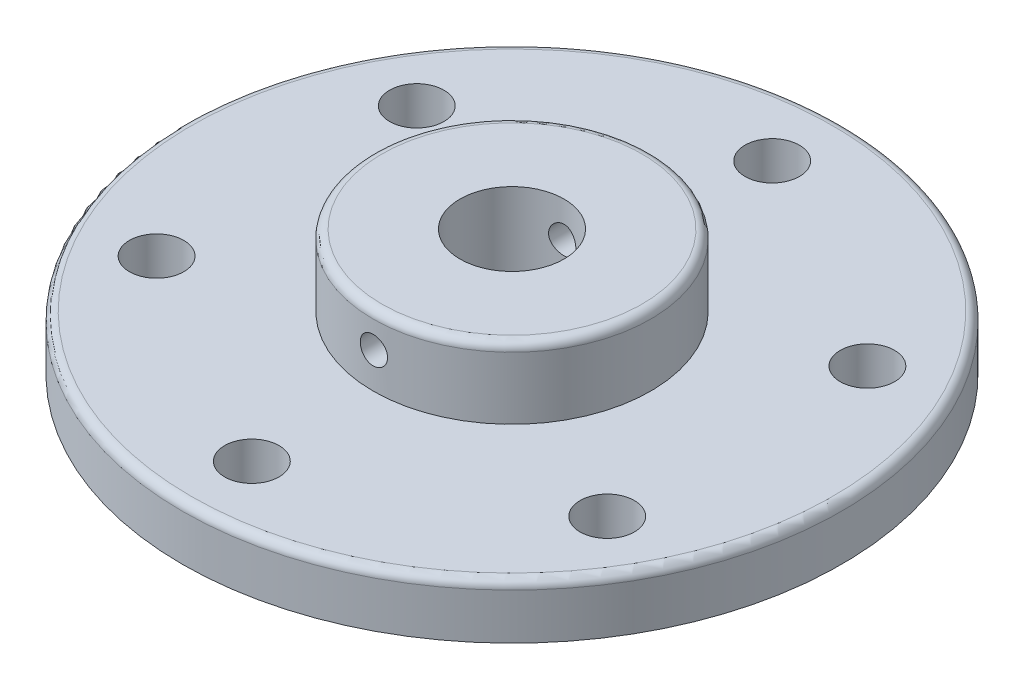
SolidWorks part; units mm, degrees
material "ABS"
ref_plane "Front Plane" through (0, 0, 0) normal (0, 0, 1) x (1, 0, 0)
ref_plane "Top Plane" through (0, 0, 0) normal (0, 1, 0) x (1, 0, 0)
ref_plane "Right Plane" through (0, 0, 0) normal (1, 0, 0) x (0, 0, -1)
sketch "Sketch1" plane through (0, 0, 0) normal (0, 1, 0) x (1, 0, 0)
  circle A0 centre (0, 0) radius 30.1625
  circle A1 centre (0, 0) radius 23.8125 construction
  circle A2 centre (0, 23.8125) radius 2.4892 construction
  circle A3 centre (0, 0) radius 12.7
  circle A4 centre (0, 0) radius 4.7625
  circle A5 centre (20.6222, 11.9063) radius 2.4892 construction
  circle A6 centre (20.6222, -11.9062) radius 2.4892 construction
  circle A7 centre (0, -23.8125) radius 2.4892 construction
  circle A8 centre (-20.6222, -11.9063) radius 2.4892 construction
  circle A9 centre (-20.6222, 11.9062) radius 2.4892 construction
  point P9 (-27.0549, 15.2885)
  point P10 (0, 0)
  point P20 (0, 0)
  dimension "D1" = 4.9784
  dimension "D2" = 47.625
  dimension "D3" = 60.325
  dimension "D4" = 9.525
  dimension "D5" = 25.4
  dimension "D6" = 6
extrude "Boss-Extrude1" add sketch "Sketch1" against normal blind 5 contours A0 A3 | A3 A4 region at (-29.3094, 0, 0) region at (-12.3408, 0, 0)
extrude "Boss-Extrude2" add sketch "Sketch1<3>" along normal blind 6.5 contours A3 A4 region at (-12.3408, 0, 0)
sketch "Sketch1<3>" plane through (0, 0, 0) normal (0, 1, 0) x (1, 0, 0) same geometry as "Sketch1"
hole_wizard "#10 Clearance Hole1" positions "3DSketch1" profile "Sketch2" hole size "#10" standard "ANSI Inch" end condition up to next
sketch3d "3DSketch1"
  point P0 (0, 0, -23.8125)
  point P2 (20.6222, 0, -11.9063)
  point P4 (20.6222, 0, 11.9062)
  point P6 (-20.6222, 0, -11.9062)
  point P8 (-20.6222, 0, 11.9063)
  point P10 (0, 0, 23.8125)
  point P13 (0, 0, -23.8125)
  point P15 (20.6222, 0, -11.9063)
  point P17 (20.6222, 0, 11.9062)
  point P19 (0, 0, 23.8125)
  point P21 (-20.6222, 0, 11.9063)
  point P23 (-20.6222, 0, -11.9062)
sketch "Sketch2" plane through (0, 0, -23.8125) normal (1, 0, 0) x (0, 0, 1)
  line L0 (0, 0) -> (0, 5)
  line L1 (0, 5) -> (2.4892, 5)
  line L2 (2.4892, 5) -> (2.4892, 0)
  line L5 (2.4892, 0) -> (0, 0)
  line L11 (0, -6.35) -> (0, 107.95) construction
  dimension "Thru Hole Dia." = 4.9784
  dimension "Thru Hole Depth" = 5
ref_plane "Plane1" through (0, 0, 12.7) normal (0, 0, 1) x (1, 0, 0)
sketch "Sketch3" plane through (0, 0, 12.7) normal (0, 0, 1) x (1, 0, 0)
  line L0 (0, 0) -> (0, 6.5)
  line L1 (30.1625, 0) -> (-30.1625, 0) construction
  line L2 (12.7, 6.5) -> (-12.7, 6.5) construction
  circle A0 centre (0, 3.25) radius 1.5
  point P6 (0, 8.9176)
  point P7 (0, 3.25)
  point P8 (0, 6.5)
  dimension "D1" = 3
hole_wizard "Tap Drill for M3x0.5 Tap1" positions "3DSketch3" profile "Sketch5" hole size "M3x0.5" standard "ANSI Metric" end condition through all
sketch3d "3DSketch3"
  point P0 (0, 3.25, 12.7)
  point P3 (0, 3.25, 12.7)
sketch "Sketch5" plane through (0, 3.25, 12.7) normal (1, 0, 0) x (0, -1, 0)
  line L0 (0, 0) -> (0, 42.8625)
  line L1 (0, 42.8625) -> (1.25, 42.8625)
  line L2 (1.25, 42.8625) -> (1.25, 0)
  line L5 (1.25, 0) -> (0, 0)
  line L11 (0, -6.35) -> (0, 107.95) construction
  dimension "Thru Hole Dia." = 2.5
  dimension "Thru Hole Depth" = 42.8625
fillet "Fillet1" radius 0.7937 2 edges at (0, 6.5, 12.7) (0, 0, 30.1625)
